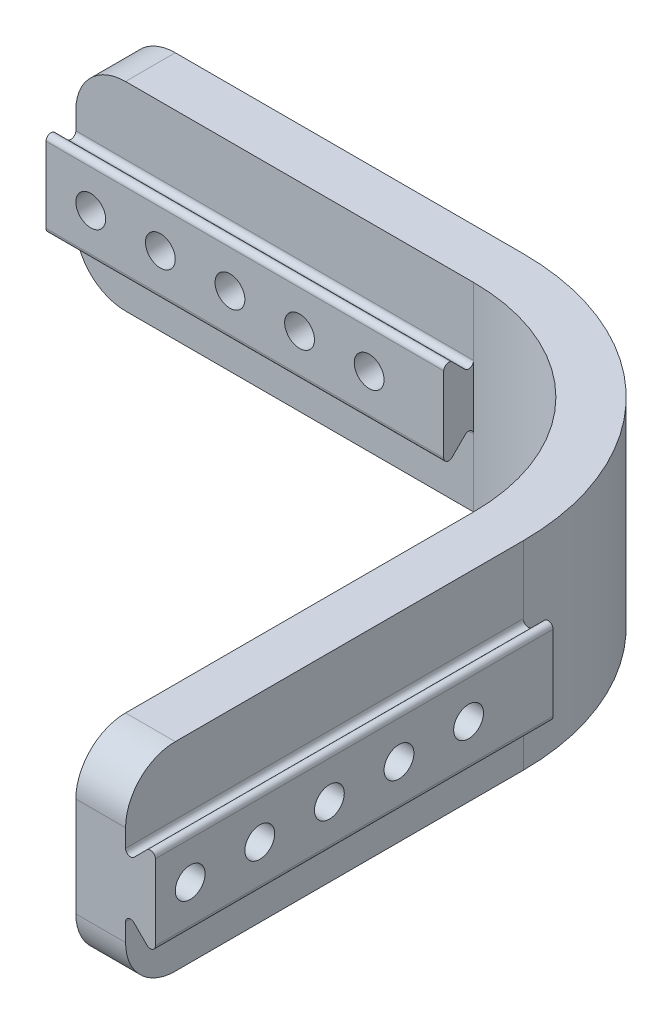
SolidWorks part; units mm, degrees
ref_plane "Front Plane" through (0, 0, 0) normal (0, 0, 1) x (1, 0, 0)
ref_plane "Top Plane" through (0, 0, 0) normal (0, 1, 0) x (1, 0, 0)
ref_plane "Right Plane" through (0, 0, 0) normal (1, 0, 0) x (0, 0, -1)
sketch "Sketch1" plane through (0, 0, 0) normal (0, 1, 0) x (1, 0, 0)
  line L0 (0, 0) -> (40, 0)
  line L1 (65, -25) -> (65, -65)
  line L2 (0, -5) -> (40, -5)
  line L3 (60, -25) -> (60, -65)
  line L4 (60, -65) -> (65, -65)
  line L5 (0, -5) -> (0, 0)
  arc A0 (40, 0) -> (65, -25) centre (40, -25) cw
  arc A1 (40, -5) -> (60, -25) centre (40, -25) cw
  dimension "D4" = 20
  dimension "D2" = 40
  dimension "D3" = 40
  dimension "D1" = 5
extrude "Boss-Extrude1" add sketch "Sketch1" along normal blind 20
sketch "Sketch2" plane through (0, 0, 0) normal (1, 0, 0) x (0, 0, -1)
  line L1 (-5, 20) -> (-5, 0) construction
  line L2 (-8, 15) -> (-8, 5)
  line L3 (-8, 5) -> (-5, 8)
  line L4 (-5, 8) -> (-5, 12)
  line L5 (-5, 10) -> (-8, 10) construction
  line L6 (-5, 12) -> (-8, 15)
  line L7 (-5, 20) -> (-25, 20) construction
  dimension "D1" = 10
  dimension "D2" = 4
  dimension "D3" = 3
  dimension "D9" = 10
extrude "Boss-Extrude2" add sketch "Sketch2" along normal blind 40
ref_plane "Plane1" through (0, 0, 65) normal (0, 0, 1) x (1, 0, 0)
sketch "Sketch3" plane through (0, 0, 65) normal (0, 0, 1) x (1, 0, 0)
  line L6 (65, 12) -> (65, 8)
  line L8 (65, 20) -> (65, 0) construction
  line L9 (65, 8) -> (68, 5)
  line L10 (68, 5) -> (68, 15)
  line L11 (68, 15) -> (65, 12)
  line L12 (65, 10) -> (68, 10) construction
  line L13 (60, 20) -> (65, 20) construction
  dimension "D1" = 10
  dimension "D2" = 4
  dimension "D3" = 3
  dimension "D4" = 10
extrude "Boss-Extrude3" add sketch "Sketch3" against normal blind 40
sketch "Sketch4" plane through (0, 0, 0) normal (1, 0, 0) x (0, 0, -1)
  line L0 (-25, 20) -> (-65, 20) construction
  line L1 (-65, 20) -> (-65, 0) construction
  circle A0 centre (-61.5, 10) radius 1.5
  dimension "D1" = 3
  dimension "D2" = 10
  dimension "D3" = 3.5
extrude "Cut-Extrude1" cut sketch "Sketch4" along normal blind 75
pattern_linear "LPattern1" count 5 spacing 7 along (0, 0, -1) of "Cut-Extrude1"
sketch "Sketch5" plane through (0, 0, 0) normal (0, 0, 1) x (1, 0, 0)
  line L0 (40, 20) -> (0, 20) construction
  line L1 (0, 20) -> (0, 0) construction
  circle A0 centre (4.5, 10) radius 1.5
  dimension "D1" = 3
  dimension "D2" = 10
  dimension "D3" = 4.5
extrude "Cut-Extrude2" cut sketch "Sketch5" along normal blind 14
pattern_linear "LPattern2" count 5 spacing 7 along (1, 0, 0) of "Cut-Extrude2"
fillet "Fillet1" radius 0.5 8 edges at (68, 5, 45) (65, 8, 45) (65, 12, 45) (68, 15, 45) (20, 8, 5) (20, 5, 8) (20, 12, 5) (20, 15, 8)
fillet "Fillet2" radius 5 4 edges at (62.5, 0, 65) (62.5, 20, 65) (0, 0, 2.5) (0, 20, 2.5)
